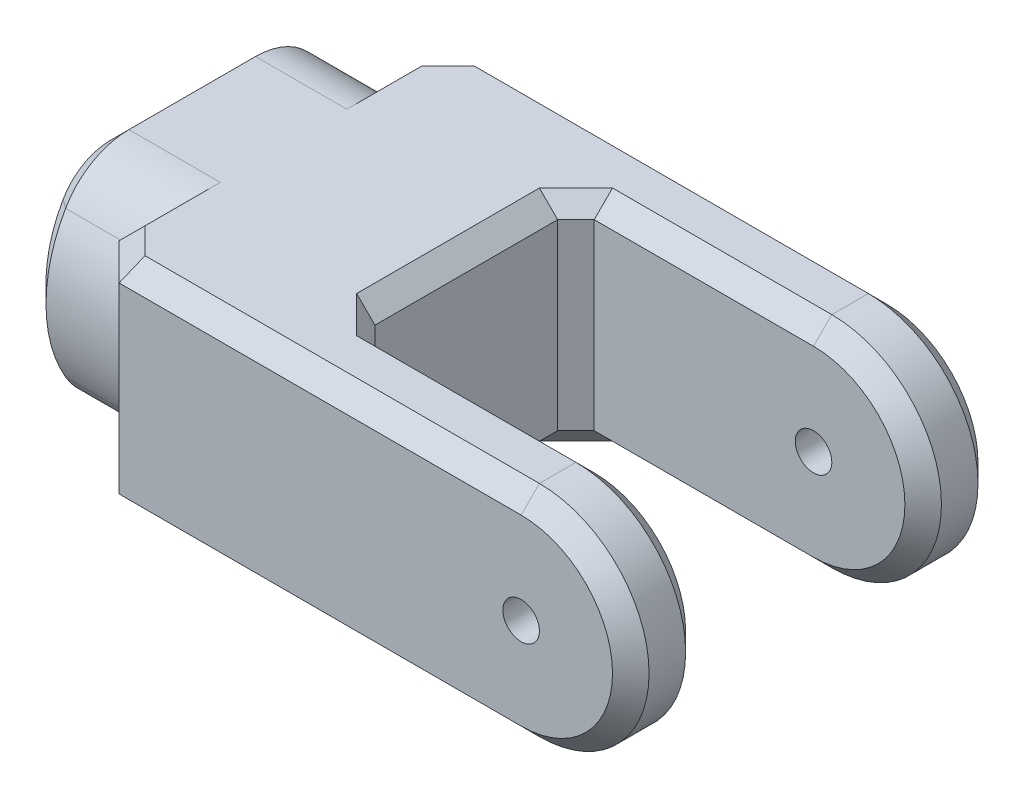
SolidWorks part; units mm, degrees
ref_plane "Front Plane" through (0, 0, 0) normal (0, 0, 1) x (1, 0, 0)
ref_plane "Top Plane" through (0, 0, 0) normal (0, 1, 0) x (1, 0, 0)
ref_plane "Right Plane" through (0, 0, 0) normal (1, 0, 0) x (0, 0, -1)
sketch "Sketch1" plane through (0, 0, 0) normal (1, 0, 0) x (0, 0, -1)
  line L0 (47.0745, 30) -> (-47.0745, 30)
  line L1 (-40.3945, -30) -> (58.4624, -30)
  circle A0 centre (0, 0) radius 25
  circle A5 centre (0, 0) radius 30
  circle A6 centre (0, 0) radius 5
  arc A7 (26.4575, -30) -> (26.4575, 30) centre (0, 0) ccw
  arc A8 (-26.4575, 30) -> (-26.4575, -30) centre (0, 0) ccw
  point P8 (0, 30)
  dimension "D1" = 60
  dimension "D2" = 50
  dimension "D3" = 10
  dimension "D4" = 10
extrude "Boss-Extrude1" add sketch "Sketch1" against normal blind 10 and the other way blind 40 contours L0 A8 L1 A5 | L1 A7 L0 A5 | A5 region at (0, 0, -39.2789) region at (0, 0, 30.7211)
extrude "Cut-Extrude1" cut sketch "Sketch1<5>" against normal blind 10 contours A6 region at (0, 0, 0)
sketch "Sketch1<5>" plane through (0, 0, 0) normal (1, 0, 0) x (0, 0, -1) same geometry as "Sketch1"
sketch "Sketch2" plane through (0, 30, 0) normal (0, 1, 0) x (1, 0, 0)
  line L0 (-154.8658, 0) -> (154.8658, 0) construction
  line L1 (15, 40) -> (25, 50)
  line L2 (40, 40) -> (-10, 40) construction
  line L3 (25, 50) -> (135, 50)
  line L4 (135, 50) -> (135, 30)
  line L5 (135, 30) -> (70, 30)
  line L6 (70, 30) -> (70, -30)
  line L7 (40, 26.4575) -> (40, -26.4575) construction
  line L8 (15, 40) -> (15, -40)
  line L9 (15, 0) -> (70, 0)
  line L10 (15, -40) -> (25, -50)
  line L11 (25, -50) -> (135, -50)
  line L12 (135, -50) -> (135, -30)
  line L13 (135, -30) -> (70, -30)
  point P4 (0, 0)
  line M9 (40, -26.4575) -> (40, 26.4575)
  line M10 (40, 26.4575) -> (-10, 26.4575)
  line M12 (-10, -26.4575) -> (40, -26.4575)
  dimension "D1" = 10
  dimension "D2" = 20
  dimension "D3" = 110
  dimension "D4" = 30
  dimension "D5" = 10
extrude "Boss-Extrude2" add sketch "Sketch2" against normal up to surface (60 mm away) contours L12 L13 L6 L9 L8 L10 L11 M9 M12 | L9 L6 L5 L4 L3 L1 L8 M9 M10 | L8 L9 M9 M10 | L9 L8 M12 M9 region at (69.1971, 30, -32.8485) region at (27.5, 30, -13.2288) region at (27.5, 30, 13.2288) region at (69.1971, 30, 32.8485) up to face at (15, -30, 0)
sketch "Sketch3" plane through (0, 0, 50) normal (0, 0, 1) x (1, 0, 0)
  line L0 (135, -30) -> (135, 30) construction
  circle A0 centre (135, 0) radius 30
  dimension "D1" = 60
extrude "Boss-Extrude3" add sketch "Sketch3" against normal up to surface (20 mm away) up to face at (102.5, 0, 30)
extrude "Boss-Extrude4" add sketch "Sketch3<2>" against normal up to surface (100 mm away) from surface up to face at (80, 0, -50) starting at face at (102.5, 0, -30)
sketch "Sketch3<2>" plane through (0, 0, 50) normal (0, 0, 1) x (1, 0, 0) same geometry as "Sketch3"
chamfer "Chamfer1" distance 5 angle 45 24 edges at (20, -30, 45) (15, -30, 33.2288) (15, -30, -33.2288) (20, -30, -45) (102.5, -30, 30) (102.5, -30, -30) (165, 0, -30) (165, 0, 30) (70, 0, 30) (70, -30, 0) (70, 0, -30) (102.5, 30, -30) (70, 30, 0) (102.5, 30, 30) (80, -30, -50) (165, 0, -50) (15, 30, -33.2288) (20, 30, -45) (80, 30, -50) (80, -30, 50) (165, 0, 50) (15, 30, 33.2288) (20, 30, 45) (80, 30, 50)
fillet "Fillet1" radius 20 4 edges at (5, -30, -26.4575) (5, -30, 26.4575) (5, 30, -26.4575) (5, 30, 26.4575)
chamfer "Chamfer2" distance 5 angle 45 9 edges at (-10, 27.3205, -27.3205) (-10, 30, 0) (-10, 27.3205, 27.3205) (-10, 0, 40) (-10, -27.3205, 27.3205) (-10, -30, 0) (-10, -27.3205, -27.3205) (-10, 0, -40) (-10, 0, -5)
sketch "Sketch4" plane through (0, 0, 50) normal (0, 0, 1) x (1, 0, 0)
  circle A0 centre (135, 0) radius 5
  dimension "D1" = 10
extrude "Cut-Extrude2" cut sketch "Sketch4" against normal through all both and the other way through all
ref_plane "Plane1" through (8.1911, -11.2741, 0) normal (0.5878, -0.809, 0) x (0, 0, -1)
sketch "Sketch5" plane through (0, 30, 0) normal (0, 1, 0) x (1, 0, 0)
  line L1 (29.9225, 17.3205) -> (50.3093, 17.3205)
  line L2 (24.9225, 12.3205) -> (24.9225, -12.3205)
  line L3 (29.9225, -17.3205) -> (50.3093, -17.3205)
  line L4 (55.3093, 12.3205) -> (55.3093, -12.3205)
  arc A0 (24.9225, -12.3205) -> (29.9225, -17.3205) centre (29.9225, -12.3205) ccw
  arc A1 (50.3093, -17.3205) -> (55.3093, -12.3205) centre (50.3093, -12.3205) ccw
  arc A2 (50.3093, 17.3205) -> (55.3093, 12.3205) centre (50.3093, 12.3205) cw
  arc A3 (29.9225, 17.3205) -> (24.9225, 12.3205) centre (29.9225, 12.3205) ccw
  dimension "D1" = 5
sketch "Sketch6" plane through (8.1911, -11.2741, 0) normal (0.5878, -0.809, 0) x (0, 0, -1)
  line L0 (0, 147.8625) -> (0, 0) construction
extrude "Boss-Extrude5" [suppressed] add sketch "Sketch5" along normal blind 20 contours L1 A3 L2 A0 L3 A1 L4 A2
chamfer "Chamfer3" [suppressed] distance 2 angle 45
